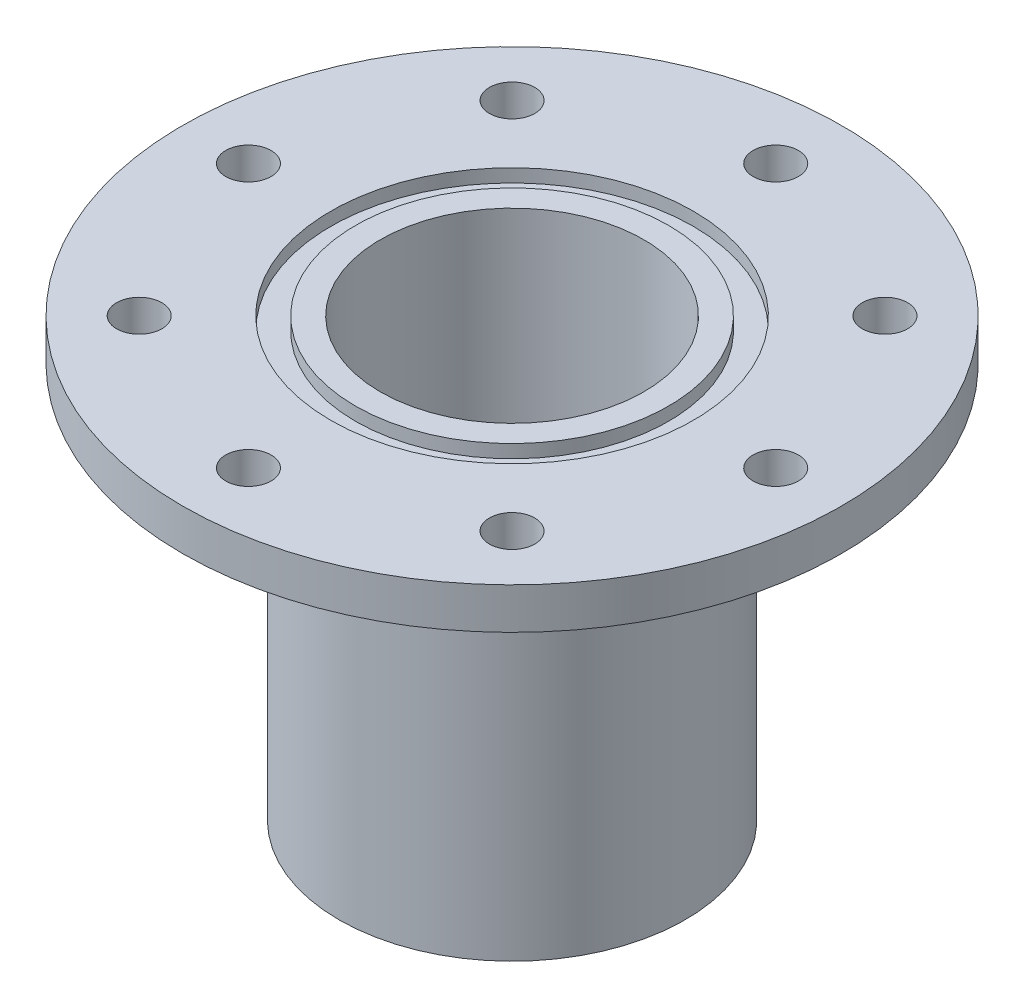
SolidWorks part; units mm, degrees
ref_plane "Front Plane" through (0, 0, 0) normal (0, 0, 1) x (1, 0, 0)
ref_plane "Top Plane" through (0, 0, 0) normal (0, 1, 0) x (1, 0, 0)
ref_plane "Right Plane" through (0, 0, 0) normal (1, 0, 0) x (0, 0, -1)
sketch "Sketch1" plane through (0, 0, 0) normal (0, 0, 1) x (1, 0, 0)
  line L0 (0, 66.3321) -> (0, -42.6625) construction
  line L1 (50.8, -152.4) -> (66.675, -152.4)
  line L2 (66.675, -152.4) -> (66.675, 0)
  line L3 (66.675, 0) -> (127, 0)
  line L4 (127, 0) -> (127, 15.875)
  line L5 (50.8, 15.875) -> (60.325, 15.875)
  line L6 (50.8, 15.875) -> (50.8, -152.4)
  line L8 (127, 15.875) -> (69.85, 15.875)
  line L9 (60.325, 15.875) -> (60.325, 10.795)
  line L10 (60.325, 10.795) -> (69.85, 10.795)
  line L11 (69.85, 15.875) -> (69.85, 10.795)
  dimension "D1" = 254
  dimension "D2" = 120.65
  dimension "D3" = 139.7
  dimension "D4" = 101.6
  dimension "D5" = 133.35
  dimension "D6" = 15.875
  dimension "D7" = 5.08
  dimension "D8" = 152.4
revolve "Revolve1" add sketch "Sketch1" angle 360 about L0
fillet "Fillet1" radius 10.16 1 edges at (0, 0, 66.675)
hole_wizard "11/16 (0.6875) Diameter Hole1" positions "Sketch3" profile "Sketch2" hole size "11/16" standard "Ansi Inch" end condition through all
sketch "Sketch3" plane through (0, 15.875, 0) normal (0, 1, 0) x (-1, 0, 0)
  point P0 (0, -101.6)
  dimension "D1" = 101.6
sketch "Sketch2" plane through (0, 15.875, -101.6) normal (1, 0, 0) x (0, 0, 1)
  line L0 (0, 0) -> (0, 168.275)
  line L1 (0, 168.275) -> (8.7312, 168.275)
  line L2 (8.7312, 168.275) -> (8.7312, 0)
  line L5 (8.7312, 0) -> (0, 0)
  line L11 (0, -6.35) -> (0, 107.95) construction
  dimension "Thru Hole Dia." = 17.4625
  dimension "Thru Hole Depth" = 168.275
ref_axis "Axis1" through (0, -152.4, 0) along (0, 1, 0)
pattern_circular "CirPattern1" count 8 over 360 about axis through (0, -152.4, 0) along (0, 1, 0) of "11/16 (0.6875) Diameter Hole1"
